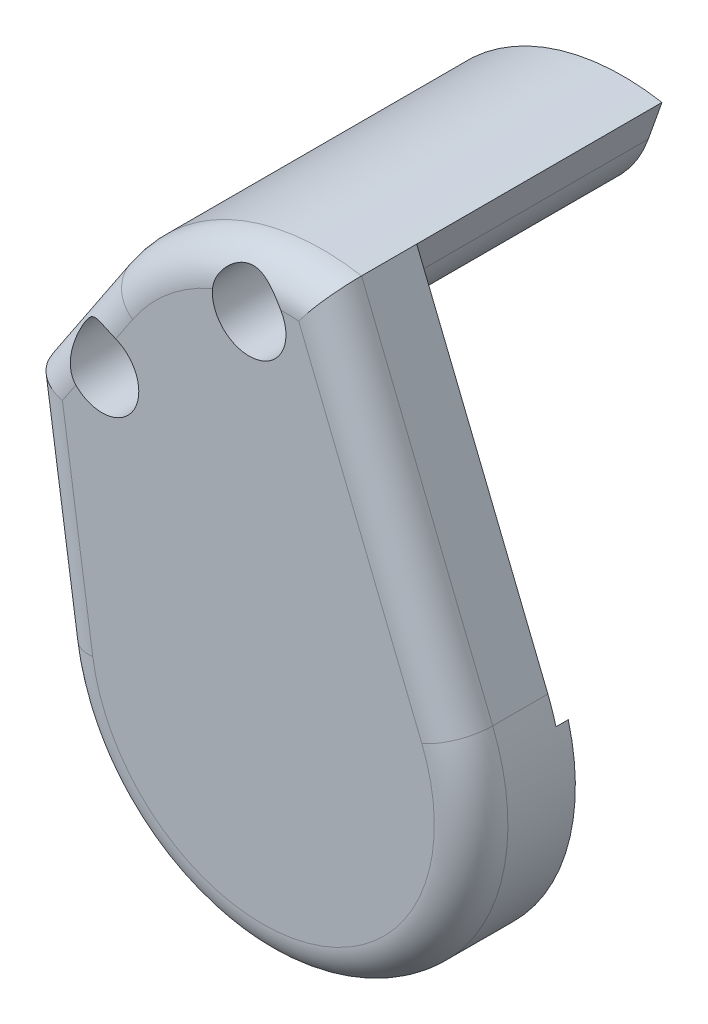
SolidWorks part; units mm, degrees
material "ABS"
ref_plane "Front Plane" through (0, 0, 0) normal (0, 0, 1) x (1, 0, 0)
ref_plane "Top Plane" through (0, 0, 0) normal (0, 1, 0) x (1, 0, 0)
ref_plane "Right Plane" through (0, 0, 0) normal (1, 0, 0) x (0, 0, -1)
sketch "Sketch1" plane through (0, 0, 0) normal (0, 0, 1) x (1, 0, 0)
  line L4 (-8.8454, 11.5206) -> (-14.8454, 2.5206)
  line L5 (-14.8454, 2.5206) -> (-14.8454, -0.4794)
  line L6 (-14.8454, -0.4794) -> (-9.8454, -0.4794)
  line L7 (-9.8454, -0.4794) -> (-8.8454, 0.5206)
  line L8 (6.839, 12.2686) -> (9.3183, 19.2686)
  arc A0 (6.839, 12.2686) -> (-8.8454, 0.5206) centre (23.5237, -26.3505) ccw
  circle A1 centre (-8.8454, 5.0206) radius 1.75
  circle A3 centre (3.1546, 15.0206) radius 1.75
  arc A4 (-8.8454, 11.5206) -> (9.3183, 19.2686) centre (6.1546, 1.5206) cw
  dimension "D15" = 3.5
  dimension "D1" = 3
  dimension "D2" = 9
  dimension "D3" = 6
  dimension "D4" = 2.4793
  dimension "D6" = 7
  dimension "D8" = 5.5
  dimension "D10" = 5
  dimension "D11" = 1
  dimension "D12" = 1
  dimension "D16" = 12
  dimension "D17" = 0
  dimension "D19" = 14.8454
  dimension "D20" = 2.5206
  dimension "D21" = 10
extrude "Boss-Extrude1" add sketch "Sketch1" along normal blind 23
fillet "Fillet3" radius 10 1 edges at (-9.8454, -0.4794, 11.5)
sketch "Sketch3" plane through (0, 0, 23) normal (0, 0, 1) x (1, 0, 0)
  line L1 (-14.8454, 2.5206) -> (-14.8454, -0.4794) construction
  line L2 (-8.8454, 11.5206) -> (-14.8454, 2.5206) construction
  line L5 (-14.8454, 2.5206) -> (-14.8454, -0.4794)
  line L6 (-8.8454, 11.5206) -> (-14.8454, 2.5206)
  line L9 (9.3183, 19.2686) -> (20.0134, -7.1628)
  line L10 (-14.8454, -0.4794) -> (-12.565, -16.0091)
  arc A2 (9.3183, 19.2686) -> (-8.8454, 11.5206) centre (6.1546, 1.5206) ccw construction
  arc A3 (-12.565, -16.0091) -> (20.0134, -7.1628) centre (4.2546, -13.5394) ccw
  circle A4 centre (3.1546, 15.0206) radius 1.75 construction
  circle A5 centre (-8.8454, 5.0206) radius 1.75 construction
  circle A6 centre (3.1546, 15.0206) radius 1.75
  circle A7 centre (-8.8454, 5.0206) radius 1.75
  arc A8 (9.3183, 19.2686) -> (-8.8454, 11.5206) centre (6.1546, 1.5206) ccw
  dimension "D2" = 17
  dimension "D1" = 19.1
  dimension "D3" = 15.5298
extrude "Boss-Extrude2" add sketch "Sketch3" against normal blind 4 and the other way blind 4.5
sketch "Sketch4" plane through (0, 0, 19) normal (0, 0, -1) x (-1, 0, 0)
  circle A0 centre (-4.2546, -13.5394) radius 11.25
  arc A1 (-20.0134, -7.1628) -> (12.565, -16.0091) centre (-4.2546, -13.5394) ccw construction
  dimension "D1" = 22.5
extrude "Cut-Extrude1" cut sketch "Sketch4" against normal blind 7
sketch "Sketch5" plane through (0, 0, 19) normal (0, 0, -1) x (-1, 0, 0)
  circle A0 centre (-4.2546, -13.5394) radius 13
  circle A1 centre (-4.2546, -13.5394) radius 11.25 construction
  dimension "D1" = 26
extrude "Cut-Extrude2" cut sketch "Sketch5" against normal blind 1.5
sketch "Sketch6" plane through (0, 0, 27.5) normal (0, 0, 1) x (1, 0, 0)
  circle A2 centre (-8.8454, 5.0206) radius 3
  circle A3 centre (3.1546, 15.0206) radius 3
  dimension "D1" = 6
  dimension "D2" = 6
extrude "Cut-Extrude3" cut sketch "Sketch6" against normal blind 12
sketch "Sketch7" plane through (0, 0, 19) normal (0, 0, -1) x (-1, 0, 0)
  line L1 (-19.3205, -15.7314) -> (-26.5212, 19.2686)
  line L2 (-26.5212, 19.2686) -> (-9.3183, 19.2686)
  line L7 (-6.839, 12.2686) -> (-9.3183, 19.2686) construction
  line L8 (-6.839, 12.2686) -> (-9.3183, 19.2686)
  line L9 (6.9699, 2.6315) -> (-2.9431, 1.2686)
  arc A0 (-19.3205, -15.7314) -> (-2.9431, 1.2686) centre (-4.4651, -13.654) cw
  arc A1 (6.9699, 2.6315) -> (-6.839, 12.2686) centre (-23.5237, -26.3505) ccw construction
  arc A2 (6.9699, 2.6315) -> (-6.839, 12.2686) centre (-23.5237, -26.3505) ccw
  dimension "D3" = 15
  dimension "D2" = 35
  dimension "D5" = 18
extrude "Cut-Extrude4" cut sketch "Sketch7" against normal blind 1
fillet "Fillet7" radius 3 5 edges at (-11.8454, 7.0206, 27.5) (-13.7052, -8.2443, 27.5) (8.7095, -29.9453, 27.5) (-0.9187, 18.1028, 27.5) (14.6659, 6.0529, 27.5)
fillet "Fillet8" radius 10 1 edges at (6.839, 12.2686, 10)
